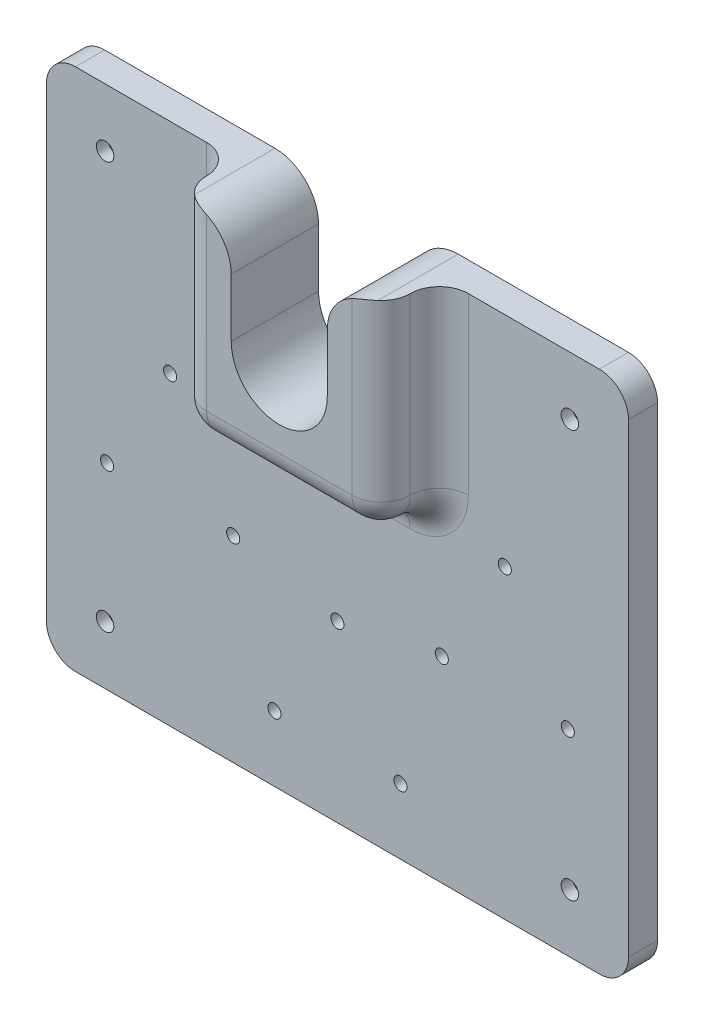
SolidWorks part; units mm, degrees
ref_plane "Front Plane" through (0, 0, 0) normal (0, 0, 1) x (1, 0, 0)
ref_plane "Top Plane" through (0, 0, 0) normal (0, 1, 0) x (1, 0, 0)
ref_plane "Right Plane" through (0, 0, 0) normal (1, 0, 0) x (0, 0, -1)
sketch "Sketch2" plane through (0, 0, 0) normal (0, 0, 1) x (1, 0, 0)
  circle A0 centre (0, 0) radius 5
  dimension "D1" = 10
sketch "Sketch1" plane through (0, 0, 0) normal (0, 0, 1) x (1, 0, 0)
  line L1 (-100, -90) -> (100, -90)
  line L2 (-100, -90) -> (-100, 90)
  line L3 (-100, 90) -> (100, 90)
  line L4 (100, -90) -> (100, 90)
  line L5 (-100, -90) -> (100, 90) construction
  line L6 (-100, 90) -> (100, -90) construction
  point P0 (0, 0)
  dimension "D1" = 200
  dimension "D2" = 180
extrude "Boss-Extrude1" add sketch "Sketch1" along normal blind 10
fillet "Fillet1" radius 10 4 edges at (-100, -90, 5) (100, -90, 5) (100, 90, 5) (-100, 90, 5)
sketch "Sketch26" plane through (0, 0, 0) normal (0, 0, -1) x (-1, 0, 0)
  line L2 (-79.85, 70) -> (79.85, 70) construction
  line L3 (-79.85, 70) -> (-79.85, -70) construction
  line L4 (-79.85, -70) -> (79.85, -70) construction
  line L5 (79.85, 70) -> (79.85, -70) construction
  line L6 (-79.85, 70) -> (79.85, -70) construction
  line L7 (-79.85, -70) -> (79.85, 70) construction
  circle A0 centre (-79.85, 70) radius 1.75
  circle A1 centre (-79.85, -70) radius 1.75
  circle A2 centre (79.85, -70) radius 1.75
  circle A3 centre (79.85, 70) radius 1.75
  point P11 (0, 0)
  dimension "D1" = 140
  dimension "D3" = 159.7
  dimension "D2" = 3.5
extrude "Cut-Extrude5" cut sketch "Sketch26" against normal through all both and the other way through all
sketch "Sketch27" plane through (0, 0, 10) normal (0, 0, 1) x (1, 0, 0)
  circle A0 centre (-79.85, 70) radius 3
  circle A1 centre (79.85, 70) radius 3
  circle A2 centre (79.85, -70) radius 3
  circle A3 centre (-79.85, -70) radius 3
  dimension "D1" = 6
extrude "Cut-Extrude6" cut sketch "Sketch27" against normal blind 4
sketch "Sketch28" plane through (0, 0, 10) normal (0, 0, 1) x (1, 0, 0)
  line L0 (90, 90) -> (-90, 90) construction
  line L1 (35, 90) -> (-35, 90)
  line L2 (35, 90) -> (35, 20)
  line L3 (35, 20) -> (-35, 20)
  line L4 (-35, 90) -> (-35, 20)
  line L5 (35, 90) -> (-35, 20) construction
  line L6 (35, 20) -> (-35, 90) construction
  point P4 (0, 55)
  dimension "D1" = 70
  dimension "D2" = 70
extrude "Boss-Extrude2" add sketch "Sketch28" along normal offset from surface (20 mm away) 30 up to face at (-81.6, 70, 0)
ref_plane "Plane1" through (0, 0, 30) normal (0, 0, 1) x (1, 0, 0)
sketch "Sketch29" plane through (0, 0, 30) normal (0, 0, 1) x (1, 0, 0)
  line L0 (-35, 20) -> (-35, 90) construction
  line L1 (-35, 20) -> (35, 20) construction
  line L2 (-16.5, 55) -> (-16.5, 90)
  line L3 (-35, 90) -> (35, 90) construction
  line L4 (16.5, 55) -> (16.5, 90)
  line L5 (16.5, 90) -> (-16.5, 90)
  circle A0 centre (0, 55) radius 16.5 construction
  arc A1 (-16.5, 55) -> (16.5, 55) centre (0, 55) ccw
  point P2 (0, 20)
  point P4 (-35, 55)
  dimension "D1" = 33
extrude "Cut-Extrude8" cut sketch "Sketch29" against normal through all both and the other way through all
fillet "Fillet3" radius 10 8 edges at (0, 20, 10) (-35, 55, 30) (0, 20, 30) (35, 55, 30) (35, 55, 10) (35, 20, 20) (-35, 20, 20) (-35, 55, 10)
fillet "Fillet4" radius 15 2 edges at (16.5, 90, 15) (-16.5, 90, 15)
sketch "Sketch30" plane through (0, 0, 10) normal (0, 0, 1) x (1, 0, 0)
  line L0 (0, -90) -> (-57.5, -10) construction
  line L1 (0, -90) -> (57.5, -10) construction
  line L2 (-90, -90) -> (90, -90) construction
  line L4 (-57.5, -10) -> (57.5, -10) construction
  point P7 (1.7178, -87.61)
  point P8 (-1.7178, -87.61)
  point P26 (0, -69.7921)
  line B0 (-21.6506, -67.5) -> (0, -30) construction
  line B1 (0, -30) -> (21.6506, -67.5) construction
  line B2 (21.6506, -67.5) -> (-21.6506, -67.5) construction
  line B3 (-21.6506, -67.5) -> (0, -55) construction
  line B4 (0, -20) -> (0, -90) construction
  line B5 (0, -30) -> (0, -55) construction
  line B6 (0, -55) -> (21.6506, -67.5) construction
  circle B7 centre (-21.6506, -67.5) radius 2.25
  circle B8 centre (21.6506, -67.5) radius 2.25
  circle B9 centre (0, -30) radius 2.25
  circle B10 centre (0, -30) radius 6.25 construction
  circle B11 centre (-21.6506, -67.5) radius 6.25 construction
  circle B12 centre (21.6506, -67.5) radius 6.25 construction
  circle B13 centre (0, -55) radius 25 construction
  circle B14 centre (0, -55) radius 31.25 construction
  line B15 (-79.1506, -22.5) -> (-57.5, 15) construction
  line B16 (-57.5, 15) -> (-35.8494, -22.5) construction
  line B17 (-35.8494, -22.5) -> (-79.1506, -22.5) construction
  line B18 (-79.1506, -22.5) -> (-57.5, -10) construction
  line B19 (-57.5, 25) -> (-57.5, -45) construction
  line B20 (-57.5, 15) -> (-57.5, -10) construction
  line B21 (-57.5, -10) -> (-35.8494, -22.5) construction
  circle B22 centre (-79.1506, -22.5) radius 2.25
  circle B23 centre (-35.8494, -22.5) radius 2.25
  circle B24 centre (-57.5, 15) radius 2.25
  circle B25 centre (-57.5, 15) radius 6.25 construction
  circle B26 centre (-79.1506, -22.5) radius 6.25 construction
  circle B27 centre (-35.8494, -22.5) radius 6.25 construction
  circle B28 centre (-57.5, -10) radius 25 construction
  circle B29 centre (-57.5, -10) radius 31.25 construction
  line B30 (35.8494, -22.5) -> (57.5, 15) construction
  line B31 (57.5, 15) -> (79.1506, -22.5) construction
  line B32 (79.1506, -22.5) -> (35.8494, -22.5) construction
  line B33 (35.8494, -22.5) -> (57.5, -10) construction
  line B34 (57.5, 25) -> (57.5, -45) construction
  line B35 (57.5, 15) -> (57.5, -10) construction
  line B36 (57.5, -10) -> (79.1506, -22.5) construction
  circle B37 centre (35.8494, -22.5) radius 2.25
  circle B38 centre (79.1506, -22.5) radius 2.25
  circle B39 centre (57.5, 15) radius 2.25
  circle B40 centre (57.5, 15) radius 6.25 construction
  circle B41 centre (35.8494, -22.5) radius 6.25 construction
  circle B42 centre (79.1506, -22.5) radius 6.25 construction
  circle B43 centre (57.5, -10) radius 25 construction
  circle B44 centre (57.5, -10) radius 31.25 construction
  dimension "D1" = 80
  dimension "D2" = 115
sketch_block_instance "Block1-1"
sketch_block "Block1" parameters "D1"=4.5, "D3"=50, "D2"=4
sketch_block_instance "Block1-2"
sketch_block_instance "Block1-3"
extrude "Cut-Extrude9" cut sketch "Sketch30" against normal through all both and the other way through all
